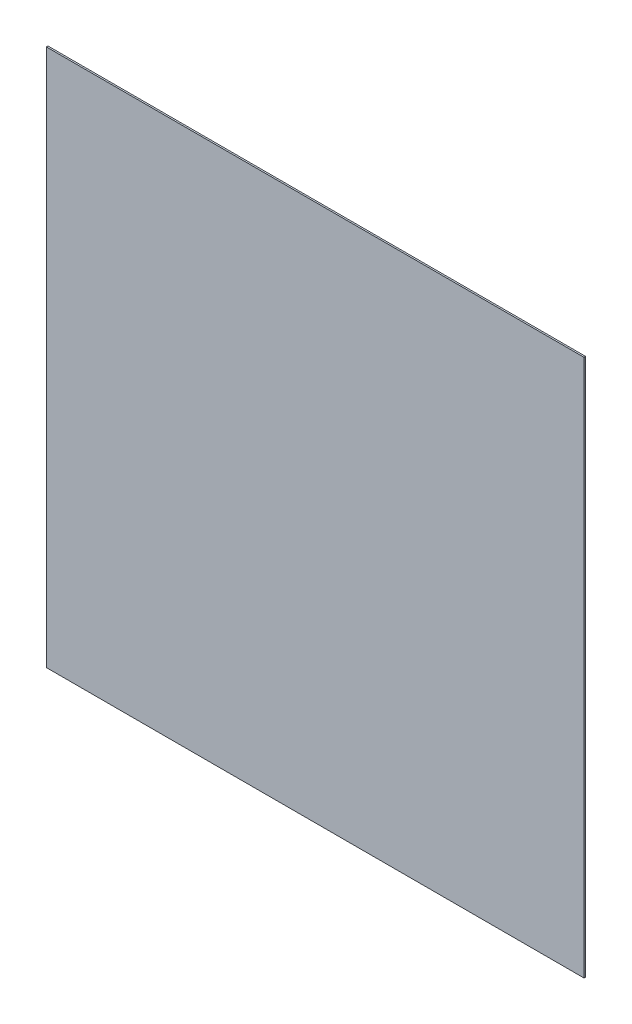
SolidWorks part; units mm, degrees
ref_plane "Front Plane" through (0, 0, 0) normal (0, 0, 1) x (1, 0, 0)
ref_plane "Top Plane" through (0, 0, 0) normal (0, 1, 0) x (1, 0, 0)
ref_plane "Right Plane" through (0, 0, 0) normal (1, 0, 0) x (0, 0, -1)
sketch "Sketch1" plane through (0, 0, 0) normal (0, 0, 1) x (1, 0, 0)
  line L1 (12.7, 374.6) -> (-387.3, 374.6)
  line L2 (12.7, 374.6) -> (12.7, -25.4)
  line L3 (12.7, -25.4) -> (-387.3, -25.4)
  line L4 (-387.3, 374.6) -> (-387.3, -25.4)
extrude "Boss-Extrude1" add sketch "Sketch1" along normal blind 1.2
